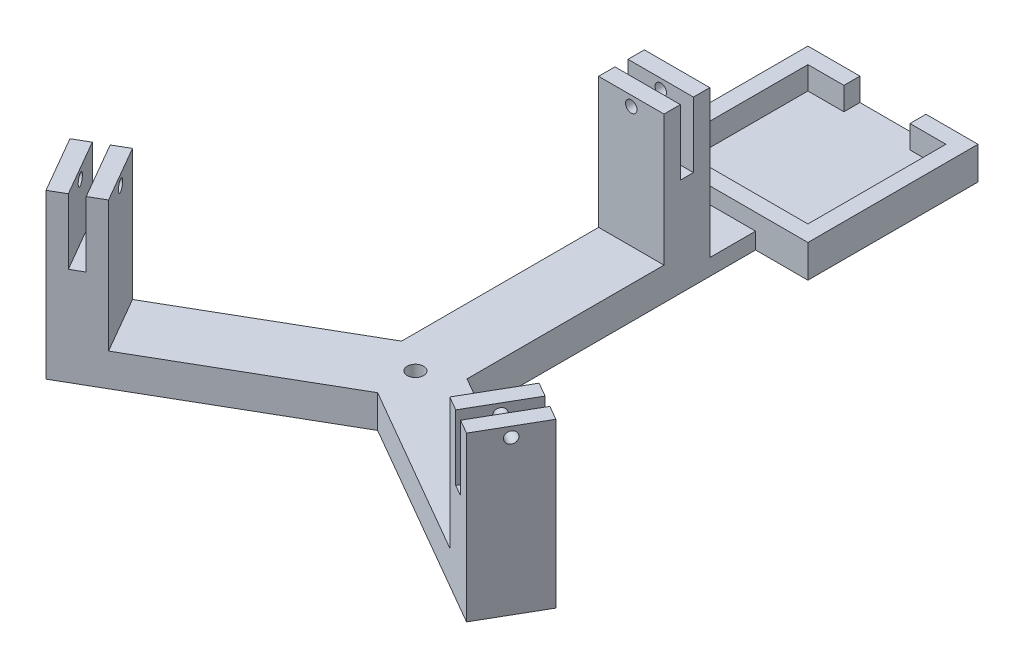
SolidWorks part; units mm, degrees
ref_plane "Front Plane" through (0, 0, 0) normal (0, 0, 1) x (1, 0, 0)
ref_plane "Top Plane" through (0, 0, 0) normal (0, 1, 0) x (1, 0, 0)
ref_plane "Right Plane" through (0, 0, 0) normal (1, 0, 0) x (0, 0, -1)
sketch "Sketch1" plane through (0, 0, 0) normal (0, 1, 0) x (1, 0, 0)
  line L0 (0, 0) -> (-10, 5.7735)
  line L1 (-10, 5.7735) -> (-10, 80)
  line L2 (-10, 80) -> (10, 80)
  line L3 (10, 80) -> (10, 5.7735)
  line L4 (10, 5.7735) -> (0, 0)
  dimension "D1" = 120
  dimension "D2" = 20
  dimension "D3" = 80
extrude "Boss-Extrude1" add sketch "Sketch1" along normal blind 10
sketch "Sketch2" plane through (0, 10, 0) normal (0, 1, 0) x (1, 0, 0)
  line L0 (10, 5.7735) -> (10, 80) construction
  line L1 (-10, 80) -> (10, 80)
  line L2 (-10, 80) -> (-10, 66)
  line L3 (-10, 66) -> (10, 66)
  line L4 (10, 80) -> (10, 66)
  dimension "D1" = 14
extrude "Boss-Extrude2" add sketch "Sketch2" along normal blind 20
sketch "Sketch3" plane through (0, 30, 0) normal (0, 1, 0) x (1, 0, 0)
  line L0 (10, 66) -> (10, 80) construction
  line L1 (-10, 80) -> (10, 80)
  line L2 (-10, 80) -> (-10, 75)
  line L3 (-10, 75) -> (10, 75)
  line L4 (10, 80) -> (10, 75)
  line L6 (-10, 66) -> (10, 66)
  line L7 (-10, 66) -> (-10, 71)
  line L8 (-10, 71) -> (10, 71)
  line L9 (10, 66) -> (10, 71)
  dimension "D1" = 5
  dimension "D2" = 5
extrude "Boss-Extrude3" add sketch "Sketch3" along normal blind 20
sketch "Sketch4" plane through (0, 0, -66) normal (0, 0, 1) x (1, 0, 0)
  line L0 (-10, 50) -> (-10, 10) construction
  line L1 (-10, 50) -> (10, 50) construction
  circle A0 centre (0, 47) radius 1.75
  dimension "D3" = 3.5
  dimension "D1" = 10
  dimension "D2" = 3
extrude "Cut-Extrude1" cut sketch "Sketch4" against normal through all both and the other way through all
pattern_circular "CirPattern1" count 3 over 360 about axis through (0, 10, 0) along (0, -1, 0) of "Boss-Extrude2", "Cut-Extrude1", "Boss-Extrude1", "Boss-Extrude3"
sketch "Sketch5" plane through (0, 10, 0) normal (0, 1, 0) x (1, 0, 0)
  circle A0 centre (0, 0) radius 2.5
  dimension "D1" = 5
extrude "Cut-Extrude2" cut sketch "Sketch5" against normal through all
sketch "Sketch6" plane through (0, 0, 0) normal (0, -1, 0) x (1, 0, 0)
  circle A0 centre (0, 0) radius 2.5 construction
  dimension "D1" = 5
sketch "Sketch8" plane through (0, 0, 0) normal (0, 1, 0) x (1, 0, 0)
  line L10 (-10, 80) -> (10, 80)
  line L11 (-10, 80) -> (-10, 94)
  line L12 (-10, 94) -> (10, 94)
  line L13 (10, 80) -> (10, 94)
  dimension "D2" = 14
  dimension "D13" = 20
sketch "Sketch11" plane through (0, 0, 0) normal (0, 1, 0) x (1, 0, 0)
  line L24 (-26, 146) -> (26, 146)
  line L25 (-26, 94) -> (-26, 146)
  line L26 (26, 146) -> (26, 94)
  line L27 (26, 94) -> (-26, 94)
  line L28 (10, 80) -> (-10, 80) construction
  line L29 (0, 0) -> (0, 94) construction
  dimension "D1" = 52
  dimension "D2" = 52
  dimension "D3" = 14
extrude "Boss-Extrude7" add sketch "Sketch8" along normal blind 5
extrude "Boss-Extrude8" add sketch "Sketch11" along normal blind 10
sketch "Sketch12" plane through (0, 10, 0) normal (0, 1, 0) x (1, 0, 0)
  line L15 (-21.1, 141.1) -> (-10.1, 141.1)
  line L16 (-21.1, 141.1) -> (-21.1, 98.9)
  line L17 (-21.1, 98.9) -> (21.1, 98.9)
  line L18 (21.1, 141.1) -> (21.1, 98.9)
  line L20 (-10.1, 141.1) -> (-10.1, 146)
  line L21 (26, 146) -> (-26, 146) construction
  line L22 (-10.1, 146) -> (10.1, 146)
  line L23 (10.1, 146) -> (10.1, 141.1)
  line L24 (10.1, 141.1) -> (21.1, 141.1)
  line L25 (0, 94) -> (0, 146) construction
  line L26 (-26, 94) -> (26, 94) construction
  dimension "D1" = 42.2
  dimension "D2" = 42.2
  dimension "D3" = 4.9
  dimension "D5" = 11
  dimension "D6" = 11
extrude "Cut-Extrude3" cut sketch "Sketch12" against normal blind 7
